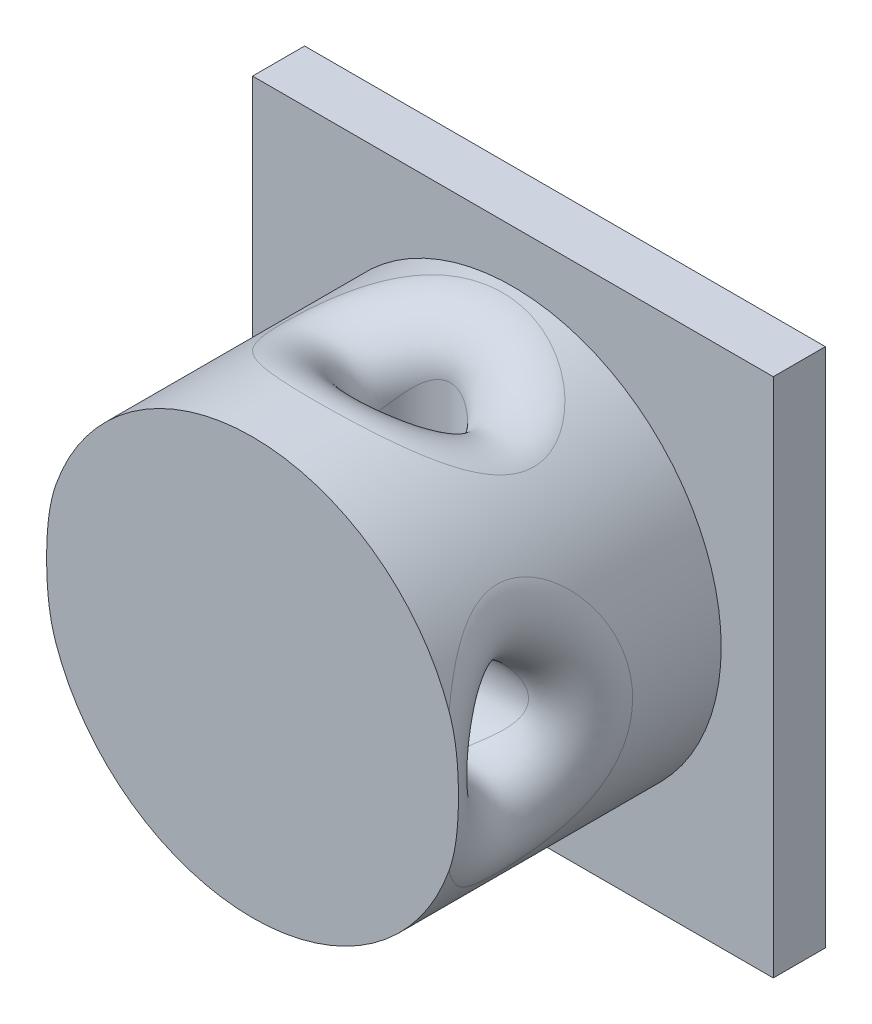
SolidWorks part; units mm, degrees
ref_plane "Alzado" through (0, 0, 0) normal (0, 0, 1) x (1, 0, 0)
ref_plane "Planta" through (0, 0, 0) normal (0, 1, 0) x (1, 0, 0)
ref_plane "Vista lateral" through (0, 0, 0) normal (1, 0, 0) x (0, 0, -1)
sketch "Croquis1" plane through (0, 0, 0) normal (0, 0, 1) x (1, 0, 0)
  line L1 (5, -5) -> (-5, -5)
  line L2 (5, -5) -> (5, 5)
  line L3 (5, 5) -> (-5, 5)
  line L4 (-5, -5) -> (-5, 5)
  line L5 (0, 5) -> (0, -5) construction
  line L6 (5, 0) -> (-5, 0) construction
  point P0 (0, 0)
  dimension "D1" = 10
  dimension "D2" = 10
extrude "Saliente-Extruir1" add sketch "Croquis1" along normal blind 1
sketch "Croquis2" plane through (0, 0, 0) normal (0, 0, 1) x (1, 0, 0)
  circle A0 centre (0, 0) radius 4
extrude "Saliente-Extruir2" add sketch "Croquis2" along normal blind 6
sketch "Croquis3" plane through (0, 0, 0) normal (0, 1, 0) x (1, 0, 0)
  line L0 (5, -1) -> (-5, -1) construction
  circle A0 centre (0, -3) radius 0.8
  dimension "D1" = 2
sketch "Croquis4" plane through (0, 0, 0) normal (1, 0, 0) x (0, 0, -1)
  line L0 (-2.2, 0) -> (-3.8, 0) construction
  line L1 (-6, 4) -> (-6, -4) construction
  circle A0 centre (-4.5, 0) radius 0.8
  dimension "D1" = 1.5
extrude "Cortar-Extruir1" cut sketch "Croquis3" against normal through all both and the other way through all
extrude "Cortar-Extruir2" cut sketch "Croquis4" against normal through all both and the other way through all
fillet "Redondeo4" radius 1 1 edges at (-0.1662, -3.9965, 2.2175)
fillet "Redondeo5" radius 1 1 edges at (0.1662, 3.9965, 2.2175)
fillet "Redondeo6" radius 1 1 edges at (3.9965, 0.1662, 5.2825)
fillet "Redondeo7" radius 1 1 edges at (-3.9965, 0.1662, 3.7175)
